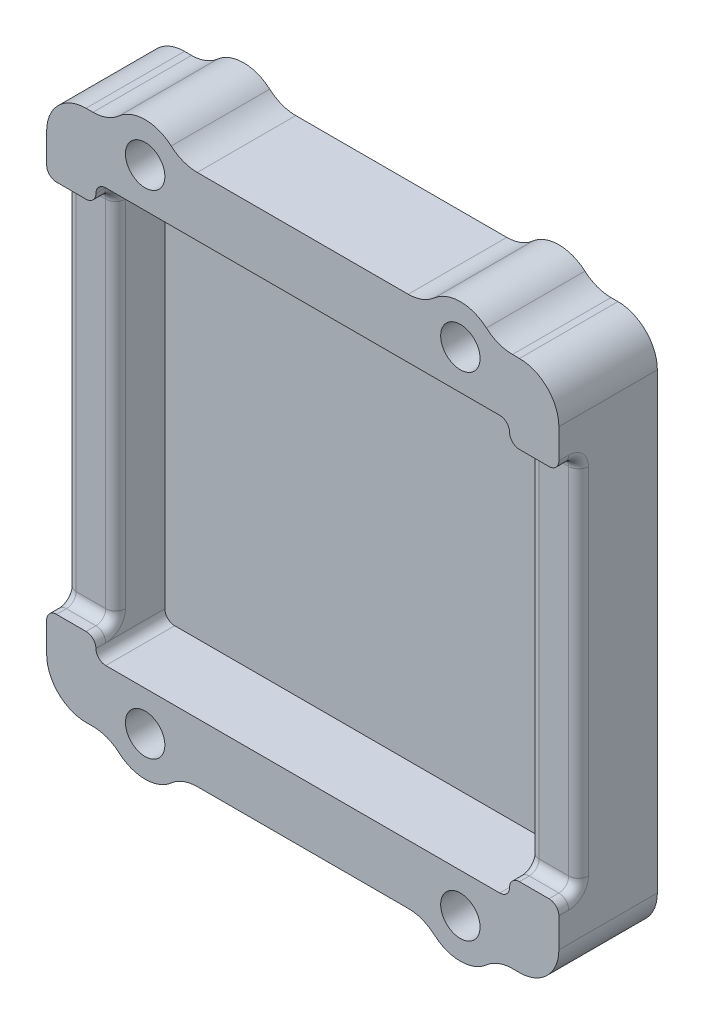
SolidWorks part; units mm, degrees
ref_plane "Plan de face" through (0, 0, 0) normal (0, 0, 1) x (1, 0, 0)
ref_plane "Plan de dessus" through (0, 0, 0) normal (0, 1, 0) x (1, 0, 0)
ref_plane "Plan de droite" through (0, 0, 0) normal (1, 0, 0) x (0, 0, -1)
sketch "Esquisse1" plane through (0, 0, 0) normal (0, 0, 1) x (1, 0, 0)
  line L0 (0, 0) -> (0, 13.5) construction
  line L1 (10.5, 10.5) -> (-10.5, 10.5)
  line L2 (10.5, 10.5) -> (10.5, -10.5)
  line L3 (10.5, -10.5) -> (-10.5, -10.5)
  line L4 (-10.5, 10.5) -> (-10.5, -10.5)
  line L5 (10.5, 10.5) -> (-10.5, -10.5) construction
  line L6 (10.5, -10.5) -> (-10.5, 10.5) construction
  line L7 (13, 13.5) -> (9.7321, 13.5)
  line L8 (13, 13.5) -> (13, -13.5)
  line L9 (13, -13.5) -> (9.7321, -13.5)
  line L10 (-13, 13.5) -> (-13, -13.5)
  line L11 (13, 13.5) -> (-13, -13.5) construction
  line L12 (13, -13.5) -> (-13, 13.5) construction
  line L13 (0, 0) -> (13, 0) construction
  line L14 (-9.7321, 13.5) -> (-13, 13.5)
  line L15 (6.2679, 13.5) -> (-6.2679, 13.5)
  line L16 (-9.7321, -13.5) -> (-13, -13.5)
  line L17 (6.2679, -13.5) -> (-6.2679, -13.5)
  circle A0 centre (-8, 12.5) radius 1
  circle A1 centre (8, 12.5) radius 1
  circle A2 centre (8, -12.5) radius 1
  circle A3 centre (-8, -12.5) radius 1
  arc A4 (-6.2679, 13.5) -> (-9.7321, 13.5) centre (-8, 12.5) ccw
  arc A5 (9.7321, 13.5) -> (6.2679, 13.5) centre (8, 12.5) ccw
  arc A6 (-9.7321, -13.5) -> (-6.2679, -13.5) centre (-8, -12.5) ccw
  arc A7 (6.2679, -13.5) -> (9.7321, -13.5) centre (8, -12.5) ccw
  point P0 (0, 0)
  point P6 (0, 0)
  dimension "D6" = 2
  dimension "D7" = 25
  dimension "D1" = 21
  dimension "D2" = 21
  dimension "D3" = 2.5
  dimension "D4" = 2.5
  dimension "D5" = 3
  dimension "D8" = 16
extrude "Boss.-Extru.1" add sketch "Esquisse1" along normal blind 5
sketch "Esquisse2" plane through (0, 0, 0) normal (0, 0, -1) x (-1, 0, 0)
  line L1 (10.5, 10.5) -> (-10.5, 10.5)
  line L2 (10.5, 10.5) -> (10.5, -10.5)
  line L3 (10.5, -10.5) -> (-10.5, -10.5)
  line L4 (-10.5, 10.5) -> (-10.5, -10.5)
  line L5 (10.5, 10.5) -> (-10.5, -10.5) construction
  line L6 (10.5, -10.5) -> (-10.5, 10.5) construction
  point P4 (0, 0)
extrude "Boss.-Extru.2" add sketch "Esquisse2" against normal blind 1.5
sketch "Esquisse3" plane through (0, 0, 5) normal (0, 0, 1) x (1, 0, 0)
  line L0 (-13, 13.5) -> (-13, -13.5) construction
  line L1 (-13, 9.5) -> (-10.5, 9.5)
  line L2 (-13, 9.5) -> (-13, -9.5)
  line L3 (-13, -9.5) -> (-10.5, -9.5)
  line L4 (-10.5, 9.5) -> (-10.5, -9.5)
  line L5 (-13, 9.5) -> (-10.5, -9.5) construction
  line L6 (-13, -9.5) -> (-10.5, 9.5) construction
  line L7 (-10.5, 10.5) -> (-10.5, -10.5) construction
  line L8 (0, 13.5) -> (0, -13.5) construction
  line L9 (6.2679, 13.5) -> (-6.2679, 13.5) construction
  line L10 (-6.2679, -13.5) -> (6.2679, -13.5) construction
  line L11 (13, -9.5) -> (10.5, 9.5) construction
  line L12 (13, 9.5) -> (10.5, -9.5) construction
  line L13 (10.5, 9.5) -> (10.5, -9.5)
  line L14 (13, -9.5) -> (10.5, -9.5)
  line L15 (13, 9.5) -> (13, -9.5)
  line L16 (13, 9.5) -> (10.5, 9.5)
  line L17 (0, 0) -> (11.75, 0) construction
  point P4 (-11.75, 0)
  point P19 (11.75, 0)
  dimension "D1" = 19
extrude "Enlèv. mat.-Extru.1" cut sketch "Esquisse3" against normal blind 1
fillet "Congé1" radius 2 4 edges at (-13, 13.5, 2.5) (-13, -13.5, 2.5) (13, -13.5, 2.5) (13, 13.5, 2.5)
fillet "Congé2" radius 2 8 edges at (-9.7321, -13.5, 2.5) (-6.2679, -13.5, 2.5) (6.2679, -13.5, 2.5) (9.7321, -13.5, 2.5) (9.7321, 13.5, 2.5) (6.2679, 13.5, 2.5) (-6.2679, 13.5, 2.5) (-9.7321, 13.5, 2.5)
fillet "Congé3" radius 0.5 20 edges at (13, -9.5, 4.5) (-13, 9.5, 4.5) (-13, -9.5, 4.5) (-10.5, -9.5, 4.5) (-10.5, 9.5, 4.5) (10.5, 9.5, 4.5) (10.5, -9.5, 4.5) (13, 0, 4) (-13, 0, 4) (-10.5, 0, 4) (10.5, 0, 4) (13, 9.5, 4.5) (11.75, -9.5, 4) (11.75, 9.5, 4) (-11.75, 9.5, 4) (-11.75, -9.5, 4) (-10.5, -10.5, 3.25) (10.5, -10.5, 3.25) (10.5, 10.5, 3.25) (-10.5, 10.5, 3.25)
